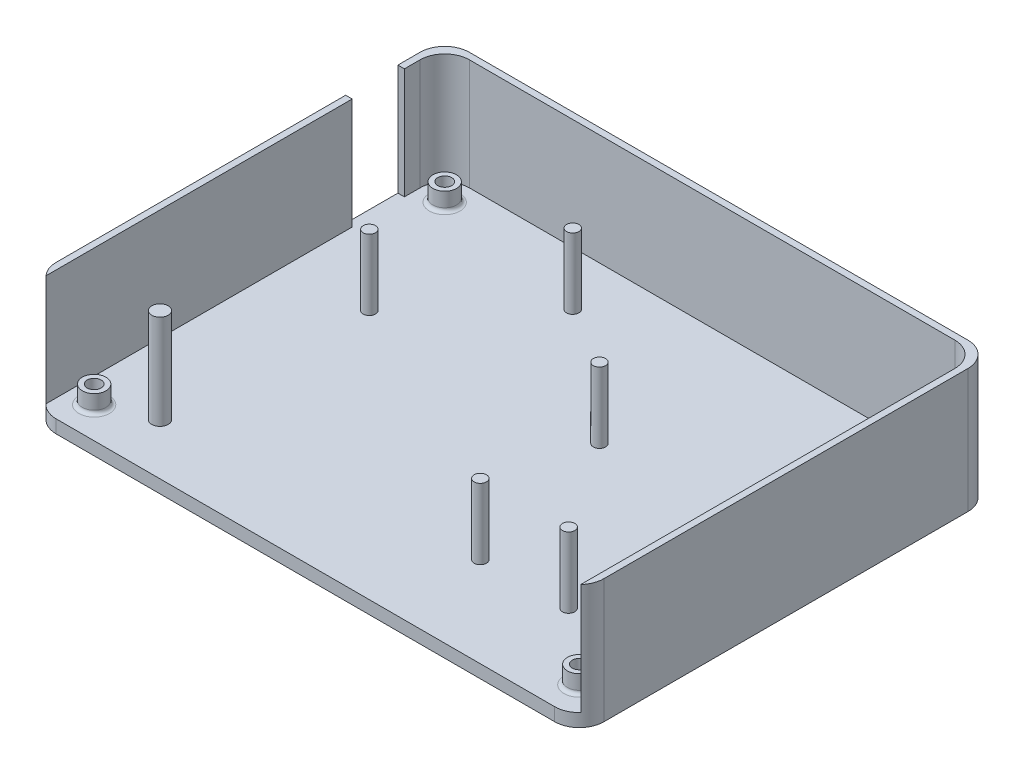
SolidWorks part; units mm, degrees
ref_plane "Front Plane" through (0, 0, 0) normal (0, 0, 1) x (1, 0, 0)
ref_plane "Top Plane" through (0, 0, 0) normal (0, 1, 0) x (1, 0, 0)
ref_plane "Right Plane" through (0, 0, 0) normal (1, 0, 0) x (0, 0, -1)
sketch "Sketch1" plane through (0, 0, 0) normal (0, 1, 0) x (1, 0, 0)
  line L0 (-66.8583, -50.2762) -> (-65.2708, -50.2762)
  line L1 (-65.2708, -50.2762) -> (64.8554, -50.2762)
  line L2 (-66.8583, -50.2762) -> (-66.8583, 44.2663)
  line L3 (-60.8583, 50.2663) -> (60.4429, 50.2663)
  line L4 (66.4429, -50.2762) -> (66.4429, 44.2663)
  line L5 (66.4429, -50.2762) -> (64.8554, -50.2762)
  line L6 (-50.3864, 41.1329) -> (-50.3864, 5.0649)
  line L7 (-50.3483, 41.1463) -> (49.9329, 41.1463)
  line L8 (-65.2708, -50.2762) -> (-65.2708, 42.6788)
  line L9 (-59.2708, 48.6788) -> (58.8554, 48.6788)
  line L10 (64.8554, -50.2762) -> (64.8554, 42.6788)
  line L11 (-50.3483, 41.1463) -> (-50.3483, -40.1162)
  line L12 (-50.3483, -40.1162) -> (49.9329, -40.1162)
  line L13 (49.9329, 41.1463) -> (49.9329, -40.1162)
  line L14 (-50.3864, 5.0649) -> (14.3836, 5.0649)
  line L15 (14.3836, 5.0649) -> (14.3836, -33.7971)
  line L16 (14.3836, -33.7971) -> (47.4036, -33.7971)
  line L17 (47.4036, -33.7971) -> (47.4036, 41.1329)
  line L18 (47.4036, 41.1329) -> (-50.3864, 41.1329)
  circle A0 centre (-59.2383, 42.6463) radius 1.7
  circle A1 centre (-59.2383, 42.6463) radius 2.875
  circle A2 centre (58.8229, 42.6463) radius 2.875
  circle A3 centre (58.8229, 42.6463) radius 1.7
  circle A4 centre (-59.2383, -42.6562) radius 2.875
  circle A5 centre (-59.2383, -42.6562) radius 1.7
  circle A6 centre (58.8229, -42.6562) radius 2.875
  circle A7 centre (58.8229, -42.6562) radius 1.7
  circle A8 centre (-21.0872, 35.6529) radius 1.5
  circle A9 centre (20.4128, -28.3471) radius 1.5
  circle A10 centre (-45.5872, 10.6529) radius 1.5
  circle A11 centre (10.4128, 10.6529) radius 1.5
  circle A12 centre (41.4128, -27.8471) radius 1.5
  arc A13 (-66.8583, 44.2663) -> (-60.8583, 50.2663) centre (-60.8583, 44.2663) cw
  arc A14 (-65.2708, 42.6788) -> (-59.2708, 48.6788) centre (-59.2708, 42.6788) cw
  circle A15 centre (-48.0512, -37.8237) radius 2
  arc A16 (58.8554, 48.6788) -> (64.8554, 42.6788) centre (58.8554, 42.6788) cw
  arc A17 (60.4429, 50.2663) -> (66.4429, 44.2663) centre (60.4429, 44.2663) cw
  point P0 (0, 0)
  point P44 (-66.8583, 50.2663)
  point P53 (66.4429, 50.2663)
  dimension "D5" = 7.62
  dimension "D7" = 7.62
  dimension "D18" = 97.79
  dimension "D20" = 64.77
  dimension "D26" = 24.5
  dimension "D32" = 6
  dimension "D33" = 6
  dimension "D34" = 6
  dimension "D1" = 133.3013
  dimension "D2" = 100.5425
  dimension "D3" = 1.5875
  dimension "D4" = 1.5875
  dimension "D6" = 7.62
  dimension "D8" = 7.62
  dimension "D9" = 7.62
  dimension "D10" = 7.62
  dimension "D11" = 7.62
  dimension "D12" = 7.62
  dimension "D13" = 1.5875
  dimension "D14" = 9.12
  dimension "D15" = 16.51
  dimension "D16" = 16.51
  dimension "D17" = 81.2625
  dimension "D19" = 36.068
  dimension "D21" = 74.93
  dimension "D22" = 5.588
  dimension "D23" = 5.588
  dimension "D24" = 7.366
  dimension "D25" = 56
  dimension "D27" = 25
  dimension "D28" = 10
  dimension "D29" = 21
  dimension "D30" = 39
  dimension "D31" = 0.5
extrude "Boss-Extrude12" add sketch "Sketch1" along normal blind 3.175 contours L5 L4 A17 L3 A13 L2 L0 L1
extrude "Boss-Extrude13" add sketch "Sketch1<23>" along normal blind 30.1625 contours L10 L5 L4 L3 L2 L0 L8 L9 region at (-66.6913, 0, 3.005)
sketch "Sketch1<23>" plane through (0, 0, 0) normal (0, 1, 0) x (1, 0, 0) same geometry as "Sketch1"
extrude "Boss-Extrude15" add sketch "Sketch1<25>" along normal blind 7.525 contours A1 A0 | A2 A3 | A6 A7 | A4 A5 region at (-62.032, 0, -42.6463) region at (56.0293, 0, -42.6463) region at (-62.032, 0, 42.6562) region at (56.0293, 0, 42.6562)
sketch "Sketch1<25>" plane through (0, 0, 0) normal (0, 1, 0) x (1, 0, 0) same geometry as "Sketch1"
extrude "Cut-Extrude3" cut sketch "Sketch1<27>" along normal blind 28.575 contours A5 | A5 | A0 | A3 | A7 region at (-59.2383, 0, 42.6562)
sketch "Sketch1<27>" plane through (0, 0, 0) normal (0, 1, 0) x (1, 0, 0) same geometry as "Sketch1"
chamfer "Chamfer2" distance 1.45 angle 45 4 edges at (58.8229, 0, 44.3562) (58.8229, 0, -40.9463) (-59.2383, 0, 44.3562) (-59.2383, 0, -40.9463)
extrude "Boss-Extrude16" add sketch "Sketch1<28>" along normal blind 20.32 contours A12 | A9 | A8 | A10 | A11 region at (20.4128, 0, 28.3471) region at (41.4128, 0, 27.8471)
sketch "Sketch1<28>" plane through (0, 0, 0) normal (0, 1, 0) x (1, 0, 0) same geometry as "Sketch1"
extrude "Boss-Extrude17" add sketch "Sketch1<29>" along normal blind 26.1874 contours A15 region at (-48.0512, 0, 37.8237)
sketch "Sketch1<29>" plane through (0, 0, 0) normal (0, 1, 0) x (1, 0, 0) same geometry as "Sketch1"
fillet "Fillet3" radius 6 2 edges at (66.4429, 15.0812, 50.2762) (-66.8583, 15.0812, 50.2762)
fillet "Fillet4" radius 0.85 1 edges at (-59.2383, 3.175, -45.5213)
fillet "Fillet5" radius 0.85 3 edges at (-59.2383, 3.175, 39.7812) (58.8229, 3.175, 39.7812) (58.8229, 3.175, -45.5213)
sketch "Sketch2" plane through (-65.2708, 0, 0) normal (1, 0, 0) x (0, 0, -1)
  line L0 (-48.3419, 3.175) -> (42.6788, 3.175) construction
  line L1 (38.8698, 3.175) -> (26.1698, 3.175)
  line L2 (38.8698, 3.175) -> (38.8698, 30.1625)
  line L3 (38.8698, 30.1625) -> (26.1698, 30.1625)
  line L4 (26.1698, 3.175) -> (26.1698, 30.1625)
  line L5 (-48.3419, 30.1625) -> (42.6788, 30.1625) construction
  line L6 (42.6788, 30.1625) -> (42.6788, 3.175) construction
  dimension "D1" = 12.7
  dimension "D2" = 3.8089
extrude "Cut-Extrude4" cut sketch "Sketch2" against normal blind 2.54
